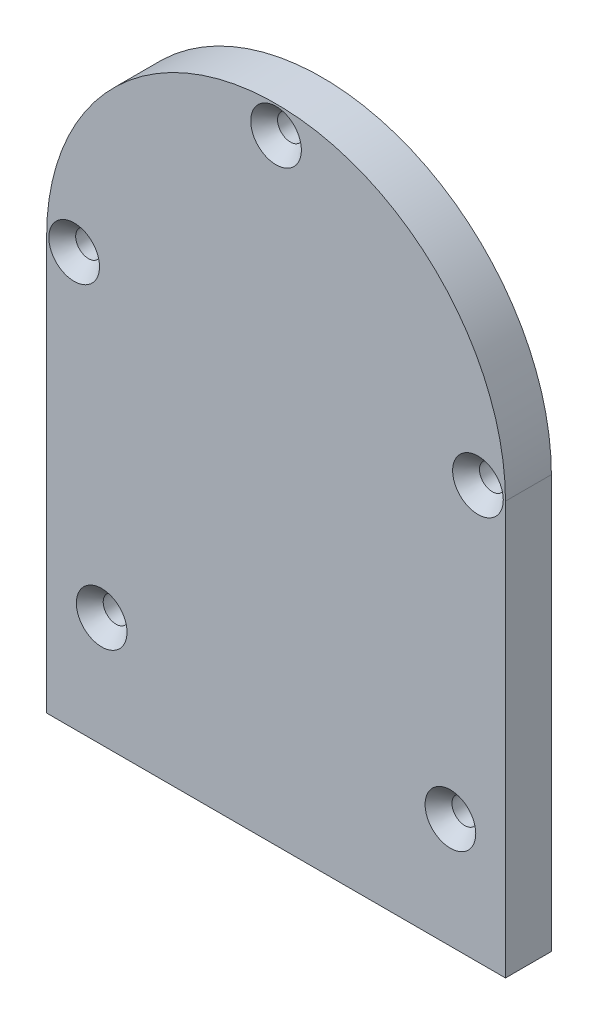
SolidWorks part; units mm, degrees
material "6061-T6 (SS)"
ref_plane "Front Plane" through (0, 0, 0) normal (0, 0, 1) x (1, 0, 0)
ref_plane "Top Plane" through (0, 0, 0) normal (0, 1, 0) x (1, 0, 0)
ref_plane "Right Plane" through (0, 0, 0) normal (1, 0, 0) x (0, 0, -1)
sketch "Sketch1" plane through (0, 0, 0) normal (0, 0, 1) x (1, 0, 0)
  line L0 (-15.875, 0) -> (-15.875, -28.575)
  line L1 (-15.875, -28.575) -> (15.875, -28.575)
  line L2 (15.875, -28.575) -> (15.875, 0)
  arc A0 (15.875, 0) -> (-15.875, 0) centre (0, 0) ccw
  dimension "D2" = 31.75
  dimension "D1" = 28.575
extrude "Boss-Extrude1" add sketch "Sketch1" along normal blind 3.175
hole_wizard "CSK for #0 Flat Head Socket Cap Screw1" positions "Sketch4" profile "Sketch3" countersink size "#0" standard "Ansi Inch" end condition through all
sketch "Sketch4" plane through (0, 0, 3.175) normal (0, 0, 1) x (1, 0, 0)
  line L0 (-15.875, -28.575) -> (15.875, -28.575) construction
  line L1 (-15.875, 0) -> (-15.875, -28.575) construction
  line L2 (15.875, -28.575) -> (15.875, 0) construction
  circle A0 centre (0, 0) radius 13.97 construction
  point P0 (0, 13.97)
  point P7 (-13.97, 0)
  point P9 (13.97, 0)
  point P11 (-12.065, -20.955)
  point P13 (12.065, -20.955)
  dimension "D1" = 27.94
  dimension "D2" = 7.62
  dimension "D3" = 3.81
  dimension "D4" = 3.81
sketch "Sketch3" plane through (0, 13.97, 3.175) normal (1, 0, 0) x (0, -1, 0)
  line L0 (0, 0) -> (0, 3.175)
  line L1 (0, 3.175) -> (0.889, 3.175)
  line L2 (0.889, 3.175) -> (0.889, 0.9935)
  line L3 (0.889, 0.9935) -> (1.7526, 0)
  line L5 (1.7526, 0) -> (0, 0)
  line L6 (-0.889, 0.9935) -> (-1.7526, 0) construction
  line L11 (0, -6.35) -> (0, 107.95) construction
  dimension "Thru Hole Dia." = 1.778
  dimension "Thru Hole Depth" = 3.175
  dimension "Near C'Sink Dia." = 3.5052
  dimension "Near C'Sink Angle" = 82
